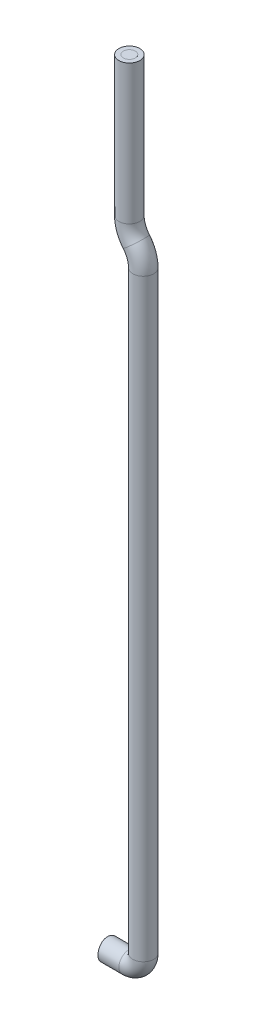
SolidWorks part; units mm, degrees
material "Изоляция провода красная"
ref_plane "Спереди" through (0, 0, 0) normal (0, 0, 1) x (1, 0, 0)
ref_plane "Сверху" through (0, 0, 0) normal (0, 1, 0) x (1, 0, 0)
ref_plane "Справа" through (0, 0, 0) normal (1, 0, 0) x (0, 0, -1)
sketch "Эскиз1" plane through (0, 0, 0) normal (0, 1, 0) x (1, 0, 0)
  circle A0 centre (0, 0) radius 1.05
  dimension "D1" = 2.1
sketch "Эскиз2" plane through (0, 0, 0) normal (0, 0, 1) x (1, 0, 0)
  line L0 (0, 0) -> (0, 50000) construction
  line L1 (0, 0) -> (0, 59.6477)
  line L2 (-3.6, 40.1771) -> (-3.6, 50040.1771) construction
  line L3 (-1.4, 62.4097) -> (0, 60.738) construction
  line L4 (-1.4, 77.5) -> (-1.4, 63.5)
  line L5 (-6.1, 56.0945) -> (-6.1, -49943.9055) construction
  arc A0 (-1.4, 63.5) -> (-0.7, 61.5739) centre (1.6, 63.5) ccw
  arc A1 (0, 59.6477) -> (-0.7, 61.5739) centre (-3, 59.6477) ccw
  point P18 (-0.7, 61.5739)
  dimension "D4" = 14
  dimension "D3" = 3
  dimension "D1" = 1.4
  dimension "D2" = 3.6
  dimension "D5" = 59.6477
  dimension "D6" = 2.5
  dimension "D7" = 39.945
sweep "По траектории1" add profiles "Эскиз1" path "Эскиз2"
sketch "Эскиз3" plane through (0, 0, 0) normal (0, -1, 0) x (1, 0, 0)
  circle A0 centre (0, 0) radius 0.6
  dimension "D1" = 1.2
sweep "Вырез-По траектории1" cut profiles "Эскиз3" path "Эскиз2<2>"
sketch "Эскиз2<2>" plane through (0, 0, 0) normal (0, 0, 1) x (1, 0, 0) same geometry as "Эскиз2"
sketch "Эскиз4" plane through (0, 0, 0) normal (0, -1, 0) x (1, 0, 0)
  circle A0 centre (0, 0) radius 0.6 construction
  circle A1 centre (0, 0) radius 0.6
sweep "По траектории2" add profiles "Эскиз4" path "Эскиз2<3>"
sketch "Эскиз2<3>" plane through (0, 0, 0) normal (0, 0, 1) x (1, 0, 0) same geometry as "Эскиз2"
sketch "Эскиз5" plane through (0, 0, 0) normal (0, -1, 0) x (1, 0, 0)
  circle A1 centre (0, 0) radius 0.6
  circle A2 centre (0, 0) radius 0.6
  dimension "D1" = 0
sketch "Эскиз6" plane through (0, 0, 0) normal (0, 0, 1) x (1, 0, 0)
  line L0 (0, 0) -> (0, -50000) construction
  line L1 (0, -1.4) -> (-50000, -1.4) construction
  line L2 (-1.05, 0) -> (1.05, 0) construction
  line L3 (-1.4, -1.4) -> (-3.6, -1.4)
  line L4 (-3.6, -1.4) -> (-3.6, 49998.6) construction
  line L5 (2.4, -1.4) -> (2.4, -50001.4) construction
  arc A0 (0, 0) -> (-1.4, -1.4) centre (-1.4, 0) cw
  dimension "D1" = 1.4
  dimension "D3" = 2.4
  dimension "D4" = 6
sweep "По траектории3" add profiles "Эскиз5" path "Эскиз6"
sketch "Эскиз7" plane through (0, 0, 0) normal (0, -1, 0) x (1, 0, 0)
  circle A0 centre (0, 0) radius 0.6 construction
  circle A1 centre (0, 0) radius 1.05
  circle A2 centre (0, 0) radius 1.05
  circle A3 centre (0, 0) radius 0.6
  dimension "D1" = 0
sweep "По траектории4" add profiles "Эскиз7" path "Эскиз6<2>"
sketch "Эскиз6<2>" plane through (0, 0, 0) normal (0, 0, 1) x (1, 0, 0) same geometry as "Эскиз6"
ref_plane "Плоскость1" through (0, -2.45, 0) normal (0, -1, 0) x (-1, 0, 0)
sketch "Эскиз8" plane through (0, -2.45, 0) normal (0, -1, 0) x (-1, 0, 0)
  line L0 (0, 0) -> (50000, 0) construction
  line L1 (3.6, -1.05) -> (3.6, 1.05) construction
  line L2 (3.6, -1.05) -> (3.6, 1.05)
  line L3 (3.6, 1.05) -> (3.5074, 1.05)
  line L5 (3.6, -1.05) -> (3.5074, -1.05)
  arc A0 (3.5074, -1.05) -> (3.5074, 1.05) centre (-2.4, 0) ccw
  dimension "D1" = 12
extrude "Вырез-Вытянуть2" cut sketch "Эскиз8" against normal blind 3 contours A0 L2 L3 region at (-3.5723, -2.45, -0.7879)
extrude "Вырез-Вытянуть3" cut sketch "Эскиз8<3>" against normal blind 3 contours A0 L5 L2 region at (-3.5723, -2.45, 0.7879)
sketch "Эскиз8<3>" plane through (0, -2.45, 0) normal (0, -1, 0) x (-1, 0, 0) same geometry as "Эскиз8"
